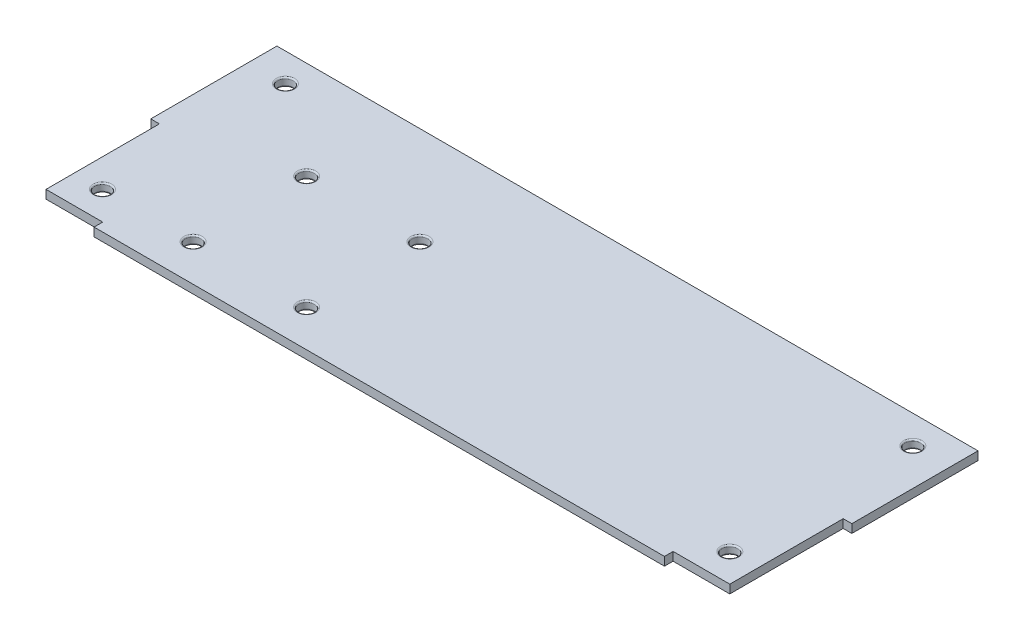
SolidWorks part; units mm, degrees
ref_plane "Front Plane" through (0, 0, 0) normal (0, 0, 1) x (1, 0, 0)
ref_plane "Top Plane" through (0, 0, 0) normal (0, 1, 0) x (1, 0, 0)
ref_plane "Right Plane" through (0, 0, 0) normal (1, 0, 0) x (0, 0, -1)
sketch "Sketch1" plane through (0, 0, 0) normal (0, 1, 0) x (1, 0, 0)
  line L1 (-123.65, -43.775) -> (123.65, -43.775)
  line L2 (-123.65, -43.775) -> (-123.65, 43.775)
  line L3 (-123.65, 43.775) -> (123.65, 43.775)
  line L4 (123.65, -43.775) -> (123.65, 43.775)
  line L5 (-123.65, -43.775) -> (123.65, 43.775) construction
  line L6 (-123.65, 43.775) -> (123.65, -43.775) construction
  point P0 (0, 0)
  dimension "D1" = 247.3
  dimension "D2" = 87.55
extrude "Boss-Extrude1" add sketch "Sketch1" along normal blind 3
sketch "Sketch4" plane through (0, 3, 0) normal (0, 1, 0) x (1, 0, 0)
  line L0 (0, 0) -> (0, -50000) construction
  line L5 (120.6, -40.725) -> (100.6, -43.775) construction
  line L15 (-123.65, -43.775) -> (-120.6, -43.775)
  line L16 (-123.65, -43.775) -> (-123.65, -0.725)
  line L21 (-123.65, -0.725) -> (-120.6, -0.725)
  line L23 (-120.6, -40.725) -> (-120.6, -0.725)
  line L24 (-123.65, -43.775) -> (-120.6, -0.725) construction
  line L25 (-123.65, -0.725) -> (-120.6, -43.775) construction
  line L34 (0, 0) -> (50000, 0) construction
  line L35 (-120.6, -43.775) -> (-100.6, -43.775)
  line L37 (-120.6, -40.725) -> (-100.6, -40.725)
  line L38 (-100.6, -43.775) -> (-100.6, -40.725)
  line L39 (-120.6, -43.775) -> (-100.6, -40.725) construction
  line L40 (-120.6, -40.725) -> (-100.6, -43.775) construction
  line L41 (120.6, -43.775) -> (100.6, -40.725) construction
  line L42 (123.65, -0.725) -> (120.6, -43.775) construction
  line L43 (123.65, -43.775) -> (120.6, -0.725) construction
  line L44 (100.6, -43.775) -> (100.6, -40.725)
  line L45 (120.6, -40.725) -> (100.6, -40.725)
  line L46 (120.6, -43.775) -> (100.6, -43.775)
  line L47 (120.6, -40.725) -> (120.6, -0.725)
  line L48 (123.65, -0.725) -> (120.6, -0.725)
  line L49 (123.65, -43.775) -> (123.65, -0.725)
  line L50 (123.65, -43.775) -> (120.6, -43.775)
  point P4 (-122.125, -22.25)
  point P9 (-110.6, -42.25)
  point P19 (110.6, -42.25)
  point P20 (122.125, -22.25)
  dimension "D1" = 43.05
  dimension "D2" = 3.05
  dimension "D3" = 3.05
  dimension "D4" = 23.05
extrude "Cut-Extrude2" cut sketch "Sketch4" against normal through all
sketch "Sketch2" plane through (0, 3, 0) normal (0, 1, 0) x (1, 0, 0)
  line L0 (0, 0) -> (50000, 0) construction
  line L1 (0, 0) -> (0, 50000) construction
  line L2 (-123.65, 43.775) -> (-123.65, -0.725) construction
  line L3 (123.65, 43.775) -> (-123.65, 43.775) construction
  line L4 (-100.6, -43.775) -> (100.6, -43.775) construction
  circle A0 centre (-110.65, 33.775) radius 2.75
  circle A1 centre (110.65, 33.775) radius 2.75
  circle A4 centre (-110.65, -30.775) radius 2.75
  circle A5 centre (110.65, -30.775) radius 2.75
  dimension "D1" = 5.5
  dimension "D2" = 13
  dimension "D3" = 10
  dimension "D4" = 13
extrude "Cut-Extrude1" cut sketch "Sketch2" against normal through all
fillet "Fillet1" radius 0.5 8 edges at (-110.65, 3, -31.025) (-110.65, 0, -31.025) (110.65, 3, -36.525) (110.65, 0, -36.525) (-110.65, 3, 33.525) (-110.65, 0, 33.525) (110.65, 3, 28.025) (110.65, 0, 28.025)
sketch "Sketch5" plane through (0, 3, 0) normal (0, 1, 0) x (1, 0, 0)
  line L5 (-10, 35.175) -> (10, 35.175)
  line L6 (15.05, 40.225) -> (15.05, 43.775)
  line L8 (-15.05, 43.775) -> (-15.05, 40.225)
  line L9 (-10, 35.225) -> (10, 35.225)
  line L10 (15, 40.225) -> (15, 92.225)
  line L11 (15, 92.225) -> (-15, 92.225)
  line L12 (-15, 92.225) -> (-15, 40.225)
  line L13 (-10, 35.225) -> (10, 35.225) construction
  line L14 (15, 40.225) -> (15, 92.225) construction
  line L15 (15, 92.225) -> (-15, 92.225) construction
  line L16 (-15, 92.225) -> (-15, 40.225) construction
  line L17 (15.05, 92.275) -> (-15.05, 92.275) construction
  line L18 (-15.05, 43.775) -> (15.05, 43.775)
  line L19 (123.65, 43.775) -> (-123.65, 43.775) construction
  line L20 (15.05, 40.225) -> (15.05, 92.275) construction
  line L21 (-15.05, 92.275) -> (-15.05, 40.225) construction
  arc A2 (10, 35.175) -> (15.05, 40.225) centre (10, 40.225) ccw
  arc A3 (-15.05, 40.225) -> (-10, 35.175) centre (-10, 40.225) ccw
  arc A4 (10, 35.225) -> (15, 40.225) centre (10, 40.225) ccw
  arc A5 (-15, 40.225) -> (-10, 35.225) centre (-10, 40.225) ccw
  arc A6 (10, 35.225) -> (15, 40.225) centre (10, 40.225) ccw construction
  arc A7 (-15, 40.225) -> (-10, 35.225) centre (-10, 40.225) ccw construction
  dimension "D1" = 0
  dimension "D2" = 0.05
extrude "Cut-Extrude3" [suppressed] cut sketch "Sketch5" against normal through all
sketch "Sketch6" [suppressed] plane through (0, 3, 0) normal (0, 1, 0) x (1, 0, 0)
  line L0 (-123.65, 105.2375) -> (-123.65, -62.1875) construction
  line L1 (-123.65, -72.4875) -> (-98.57, -72.4875)
  line L2 (-123.65, -72.4875) -> (-123.65, -8.8875)
  line L3 (-123.65, -8.8875) -> (-98.57, -8.8875)
  line L4 (-95.57, -69.4875) -> (-95.57, -11.8875)
  line L5 (-100.6, -105.2375) -> (100.6, -105.2375) construction
  line L6 (0, 0) -> (0, -50000) construction
  line L7 (95.57, -69.4875) -> (95.57, -11.8875)
  line L8 (123.65, -8.8875) -> (98.57, -8.8875)
  line L9 (123.65, -72.4875) -> (123.65, -8.8875)
  line L10 (123.65, -72.4875) -> (98.57, -72.4875)
  arc A0 (98.57, -72.4875) -> (95.57, -69.4875) centre (98.57, -69.4875) cw
  arc A1 (95.57, -11.8875) -> (98.57, -8.8875) centre (98.57, -11.8875) cw
  arc A2 (-98.57, -72.4875) -> (-95.57, -69.4875) centre (-98.57, -69.4875) ccw
  arc A3 (-95.57, -11.8875) -> (-98.57, -8.8875) centre (-98.57, -11.8875) ccw
  point P17 (95.57, -72.4875)
  point P20 (95.57, -8.8875)
  point P23 (-95.57, -72.4875)
  point P26 (-95.57, -8.8875)
  dimension "D4" = 3
  dimension "D1" = 32.75
  dimension "D2" = 63.6
  dimension "D3" = 28.08
extrude "Cut-Extrude4" [suppressed] cut sketch "Sketch6" against normal through all
sketch "Sketch8" [suppressed] plane through (0, 3, 0) normal (0, 1, 0) x (1, 0, 0)
  line L0 (-14.35, -33.2375) -> (-14.35, 49966.7625) construction
  line L1 (53.65, -55.2375) -> (-82.35, -55.2375) construction
  line L2 (53.65, -55.2375) -> (53.65, -11.2375) construction
  line L3 (53.65, -11.2375) -> (-82.35, -11.2375) construction
  line L4 (-82.35, -55.2375) -> (-82.35, -11.2375) construction
  line L5 (53.65, -55.2375) -> (-82.35, -11.2375) construction
  line L6 (53.65, -11.2375) -> (-82.35, -55.2375) construction
  line L7 (-14.35, -33.2375) -> (-50014.35, -33.2375) construction
  circle A0 centre (19.65, -55.2375) radius 1
  circle A1 centre (-14.35, -55.2375) radius 1
  circle A2 centre (-48.35, -55.2375) radius 1
  circle A3 centre (-48.35, -11.2375) radius 1
  circle A4 centre (-14.35, -11.2375) radius 1
  circle A5 centre (19.65, -11.2375) radius 1
  point P4 (-14.35, -33.2375)
  dimension "D1" = 2
  dimension "D3" = 34
extrude "Cut-Extrude6" [suppressed] cut sketch "Sketch8" against normal through all
fillet "Fillet2" [suppressed] radius 0.5
sketch "Sketch9" [suppressed] plane through (0, 3, 0) normal (0, 1, 0) x (1, 0, 0)
  circle A2 centre (-74.85, 26.2625) radius 2.75 construction
  circle A5 centre (40.15, 26.2625) radius 2.75 construction
  circle A8 centre (-74.85, 26.2625) radius 2.75
  circle A11 centre (40.15, 26.2625) radius 2.75
extrude "Cut-Extrude7" [suppressed] cut sketch "Sketch9" against normal through all
fillet "Fillet3" [suppressed] radius 0.5
sketch "Sketch10" [suppressed] plane through (0, 3, 0) normal (0, 1, 0) x (1, 0, 0)
  circle A0 centre (74.85, 49.2625) radius 2.75 construction
  circle A1 centre (-40.15, 49.2625) radius 2.75 construction
  circle A2 centre (74.85, 49.2625) radius 2.75
  circle A3 centre (-40.15, 49.2625) radius 2.75
extrude "Cut-Extrude8" [suppressed] cut sketch "Sketch10" against normal through all
fillet "Fillet4" [suppressed] radius 0.5
sketch "Sketch11" plane through (0, 3, 0) normal (0, 1, 0) x (1, 0, 0)
  line L0 (-123.65, 43.775) -> (-123.65, -0.725) construction
  line L1 (-83.65, 14.225) -> (-33.65, 14.225)
  line L6 (-83.65, 14.225) -> (-83.65, -35.775)
  line L8 (-83.65, -35.775) -> (-33.65, -35.775)
  line L9 (-33.65, 14.225) -> (-33.65, -35.775)
  line L10 (-83.65, 14.225) -> (-33.65, -35.775) construction
  line L11 (-83.65, -35.775) -> (-33.65, 14.225) construction
  circle A8 centre (-78.65, -30.775) radius 2.75
  circle A9 centre (-110.65, -30.775) radius 2.75 construction
  circle A10 centre (-110.65, -30.775) radius 2.75 construction
  circle A11 centre (-78.65, 9.225) radius 2.75
  circle A12 centre (-38.65, 9.225) radius 2.75
  circle A13 centre (-38.65, -30.775) radius 2.75
  point P4 (-58.65, -10.775)
  point P9 (-73.2634, 24.1889)
  point P21 (-58.65, -10.775)
  dimension "D3" = 5
  dimension "D4" = 5.5
  dimension "D1" = 50
  dimension "D2" = 40
  dimension "D5" = 4
extrude "Cut-Extrude9" cut sketch "Sketch11" against normal through all contours A11 | A8 | A13 | A12 region at (-78.65, 3, 30.775) region at (-78.65, 3, -9.225) region at (-38.65, 3, -9.225) region at (-38.65, 3, 30.775)
fillet "Fillet5" radius 0.5 8 edges at (-78.65, 3, -6.475) (-78.65, 0, -6.475) (-78.65, 3, 33.525) (-78.65, 0, 33.525) (-38.65, 3, 33.525) (-38.65, 0, 33.525) (-38.65, 3, -6.475) (-38.65, 0, -6.475)
sketch "Sketch12" [suppressed] plane through (0, 0, 0) normal (0, -1, 0) x (1, 0, 0)
  line L0 (0, 0) -> (0, 50000) construction
  line L4 (98.625, -155.4145) -> (122.675, -155.4145)
  line L5 (125.675, -152.4145) -> (125.675, -94.9145)
  line L6 (122.675, -91.9145) -> (98.625, -91.9145)
  line L7 (95.625, -94.9145) -> (95.625, -152.4145)
  line L9 (125.675, -105.2375) -> (125.675, -94.9145) construction
  line L10 (122.675, -91.9145) -> (98.625, -91.9145) construction
  line L11 (95.625, -94.9145) -> (95.625, -105.2375) construction
  line L12 (123.65, -105.2375) -> (-123.65, -105.2375) construction
  line L13 (123.65, -105.2375) -> (-123.65, -105.2375) construction
  line L15 (125.725, -105.2375) -> (125.725, -94.9145)
  line L16 (122.675, -91.8645) -> (98.625, -91.8645)
  line L17 (95.575, -94.9145) -> (95.575, -105.2375)
  line L18 (95.625, -105.2375) -> (125.675, -105.2375) construction
  line L19 (95.575, -105.2875) -> (125.725, -105.2875) construction
  line L20 (95.575, -105.2375) -> (125.725, -105.2375)
  line L21 (125.725, -105.2875) -> (125.725, -94.9145) construction
  line L22 (95.575, -94.9145) -> (95.575, -105.2875) construction
  line L23 (95.625, -152.4145) -> (95.625, -94.9145) construction
  line L24 (-95.625, -94.9145) -> (-95.625, -105.2375) construction
  line L25 (-122.675, -91.9145) -> (-98.625, -91.9145) construction
  line L26 (-125.675, -105.2375) -> (-125.675, -94.9145) construction
  line L27 (-95.575, -105.2375) -> (-125.725, -105.2375)
  line L28 (-95.575, -94.9145) -> (-95.575, -105.2375)
  line L29 (-122.675, -91.8645) -> (-98.625, -91.8645)
  line L30 (-125.725, -105.2375) -> (-125.725, -94.9145)
  arc A0 (125.725, -94.9145) -> (122.675, -91.8645) centre (122.675, -94.9145) ccw
  arc A1 (98.625, -91.8645) -> (95.575, -94.9145) centre (98.625, -94.9145) ccw
  arc A2 (-98.625, -91.9145) -> (-95.625, -94.9145) centre (-98.625, -94.9145) cw construction
  arc A3 (-125.675, -94.9145) -> (-122.675, -91.9145) centre (-122.675, -94.9145) cw construction
  arc A4 (122.675, -155.4145) -> (125.675, -152.4145) centre (122.675, -152.4145) ccw
  arc A5 (125.675, -94.9145) -> (122.675, -91.9145) centre (122.675, -94.9145) ccw
  arc A6 (98.625, -91.9145) -> (95.625, -94.9145) centre (98.625, -94.9145) ccw
  arc A7 (95.625, -152.4145) -> (98.625, -155.4145) centre (98.625, -152.4145) ccw
  arc A9 (125.675, -94.9145) -> (122.675, -91.9145) centre (122.675, -94.9145) ccw construction
  arc A10 (98.625, -91.9145) -> (95.625, -94.9145) centre (98.625, -94.9145) ccw construction
  arc A12 (-98.625, -91.8645) -> (-95.575, -94.9145) centre (-98.625, -94.9145) cw
  arc A13 (-125.725, -94.9145) -> (-122.675, -91.8645) centre (-122.675, -94.9145) cw
  dimension "D1" = 0
  dimension "D2" = 0.05
extrude "Cut-Extrude10" [suppressed] cut sketch "Sketch12" against normal through all
sketch "Sketch13" [suppressed] plane through (0, 0, 0) normal (0, -1, 0) x (1, 0, 0)
  line L0 (122.675, -35.1105) -> (98.625, -35.1105) construction
  line L1 (95.625, -38.1105) -> (95.625, -95.6105) construction
  line L2 (98.625, -98.6105) -> (122.675, -98.6105) construction
  line L3 (125.675, -95.6105) -> (125.675, -38.1105) construction
  line L4 (-98.625, -35.1105) -> (-122.675, -35.1105) construction
  line L5 (-125.675, -38.1105) -> (-125.675, -95.6105) construction
  line L6 (-122.675, -98.6105) -> (-98.625, -98.6105) construction
  line L7 (-95.625, -95.6105) -> (-95.625, -38.1105) construction
  line L8 (122.675, -35.1105) -> (98.625, -35.1105) construction
  line L9 (95.625, -38.1105) -> (95.625, -95.6105) construction
  line L10 (98.625, -98.6105) -> (122.675, -98.6105) construction
  line L11 (125.675, -95.6105) -> (125.675, -38.1105) construction
  line L12 (-98.625, -35.1105) -> (-122.675, -35.1105) construction
  line L13 (-125.675, -38.1105) -> (-125.675, -95.6105) construction
  line L14 (-122.675, -98.6105) -> (-98.625, -98.6105) construction
  line L15 (-95.625, -95.6105) -> (-95.625, -38.1105) construction
  line L16 (122.675, -35.0605) -> (98.625, -35.0605)
  line L17 (95.575, -38.1105) -> (95.575, -95.6105)
  line L18 (98.625, -98.6605) -> (122.675, -98.6605)
  line L19 (125.725, -95.6105) -> (125.725, -38.1105)
  line L20 (-98.625, -35.0605) -> (-122.675, -35.0605)
  line L21 (-125.725, -38.1105) -> (-125.725, -95.6105)
  line L22 (-122.675, -98.6605) -> (-98.625, -98.6605)
  line L23 (-95.575, -95.6105) -> (-95.575, -38.1105)
  arc A0 (98.625, -35.1105) -> (95.625, -38.1105) centre (98.625, -38.1105) ccw construction
  arc A1 (95.625, -95.6105) -> (98.625, -98.6105) centre (98.625, -95.6105) ccw construction
  arc A2 (122.675, -98.6105) -> (125.675, -95.6105) centre (122.675, -95.6105) ccw construction
  arc A3 (125.675, -38.1105) -> (122.675, -35.1105) centre (122.675, -38.1105) ccw construction
  arc A4 (-122.675, -35.1105) -> (-125.675, -38.1105) centre (-122.675, -38.1105) ccw construction
  arc A5 (-125.675, -95.6105) -> (-122.675, -98.6105) centre (-122.675, -95.6105) ccw construction
  arc A6 (-98.625, -98.6105) -> (-95.625, -95.6105) centre (-98.625, -95.6105) ccw construction
  arc A7 (-95.625, -38.1105) -> (-98.625, -35.1105) centre (-98.625, -38.1105) ccw construction
  arc A8 (98.625, -35.1105) -> (95.625, -38.1105) centre (98.625, -38.1105) ccw construction
  arc A9 (95.625, -95.6105) -> (98.625, -98.6105) centre (98.625, -95.6105) ccw construction
  arc A10 (122.675, -98.6105) -> (125.675, -95.6105) centre (122.675, -95.6105) ccw construction
  arc A11 (125.675, -38.1105) -> (122.675, -35.1105) centre (122.675, -38.1105) ccw construction
  arc A12 (-122.675, -35.1105) -> (-125.675, -38.1105) centre (-122.675, -38.1105) ccw construction
  arc A13 (-125.675, -95.6105) -> (-122.675, -98.6105) centre (-122.675, -95.6105) ccw construction
  arc A14 (-98.625, -98.6105) -> (-95.625, -95.6105) centre (-98.625, -95.6105) ccw construction
  arc A15 (-95.625, -38.1105) -> (-98.625, -35.1105) centre (-98.625, -38.1105) ccw construction
  arc A16 (98.625, -35.0605) -> (95.575, -38.1105) centre (98.625, -38.1105) ccw
  arc A17 (95.575, -95.6105) -> (98.625, -98.6605) centre (98.625, -95.6105) ccw
  arc A18 (122.675, -98.6605) -> (125.725, -95.6105) centre (122.675, -95.6105) ccw
  arc A19 (125.725, -38.1105) -> (122.675, -35.0605) centre (122.675, -38.1105) ccw
  arc A20 (-122.675, -35.0605) -> (-125.725, -38.1105) centre (-122.675, -38.1105) ccw
  arc A21 (-125.725, -95.6105) -> (-122.675, -98.6605) centre (-122.675, -95.6105) ccw
  arc A22 (-98.625, -98.6605) -> (-95.575, -95.6105) centre (-98.625, -95.6105) ccw
  arc A23 (-95.575, -38.1105) -> (-98.625, -35.0605) centre (-98.625, -38.1105) ccw
  dimension "D1" = 0.05
extrude "Cut-Extrude11" [suppressed] cut sketch "Sketch13" against normal through all
sketch "Sketch14" [suppressed] plane through (0, 3, 0) normal (0, 1, 0) x (1, 0, 0)
  line L0 (-123.65, 35.2205) -> (-123.65, -42.1875) construction
  line L1 (-96.15, 11.5165) -> (-91.15, 11.5165)
  line L2 (-101.15, 6.5165) -> (-101.15, -13.4835)
  line L3 (-96.15, -18.4835) -> (-91.15, -18.4835)
  line L4 (-86.15, 6.5165) -> (-86.15, -13.4835)
  line L5 (-101.15, 11.5165) -> (-86.15, -18.4835) construction
  line L6 (-101.15, -18.4835) -> (-86.15, 11.5165) construction
  line L7 (0, -1.65) -> (0, 1.65) construction
  line L8 (101.15, -18.4835) -> (86.15, 11.5165) construction
  line L9 (101.15, 11.5165) -> (86.15, -18.4835) construction
  line L10 (86.15, 6.5165) -> (86.15, -13.4835)
  line L11 (96.15, -18.4835) -> (91.15, -18.4835)
  line L12 (101.15, 6.5165) -> (101.15, -13.4835)
  line L13 (96.15, 11.5165) -> (91.15, 11.5165)
  arc A0 (-101.15, -13.4835) -> (-96.15, -18.4835) centre (-96.15, -13.4835) ccw
  arc A1 (-91.15, -18.4835) -> (-86.15, -13.4835) centre (-91.15, -13.4835) ccw
  arc A2 (-86.15, 6.5165) -> (-91.15, 11.5165) centre (-91.15, 6.5165) ccw
  arc A3 (-96.15, 11.5165) -> (-101.15, 6.5165) centre (-96.15, 6.5165) ccw
  arc A4 (96.15, 11.5165) -> (101.15, 6.5165) centre (96.15, 6.5165) cw
  arc A5 (86.15, 6.5165) -> (91.15, 11.5165) centre (91.15, 6.5165) cw
  arc A6 (91.15, -18.4835) -> (86.15, -13.4835) centre (91.15, -13.4835) cw
  arc A7 (101.15, -13.4835) -> (96.15, -18.4835) centre (96.15, -13.4835) cw
  point P4 (-93.65, -3.4835)
  point P7 (-123.65, -3.4835)
  point P38 (123.65, -3.4835)
  point P39 (93.65, -3.4835)
  dimension "D4" = 5
  dimension "D1" = 30
  dimension "D2" = 15
  dimension "D3" = 30
extrude "Cut-Extrude12" [suppressed] cut sketch "Sketch14" against normal through all
